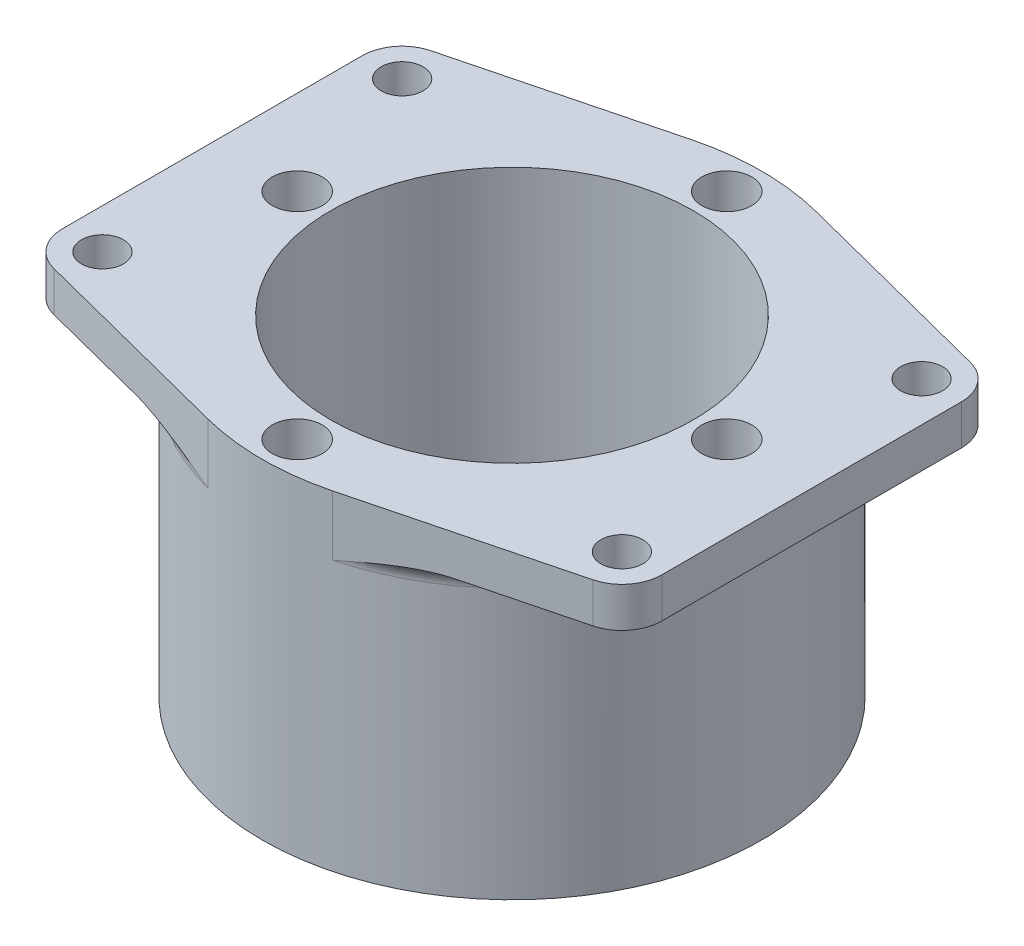
SolidWorks part; units mm, degrees
ref_plane "Front Plane" through (0, 0, 0) normal (0, 0, 1) x (1, 0, 0)
ref_plane "Top Plane" through (0, 0, 0) normal (0, 1, 0) x (1, 0, 0)
ref_plane "Right Plane" through (0, 0, 0) normal (1, 0, 0) x (0, 0, -1)
sketch "Sketch1" plane through (0, 0, 0) normal (0, 1, 0) x (1, 0, 0)
  circle A0 centre (0, 0) radius 25
  circle A1 centre (0, 0) radius 18.15 construction
  circle A2 centre (0, 0) radius 14 construction
  circle A3 centre (0, 14) radius 2.1
  circle A4 centre (14, 0) radius 2.1
  circle A5 centre (0, -14) radius 2.1
  circle A6 centre (-14, 0) radius 2.1
  point P16 (0, 0)
  dimension "D1" = 36.3
  dimension "D2" = 50
  dimension "D4" = 4.2
  dimension "D5" = 28
  dimension "D3" = 4
extrude "Boss-Extrude1" add sketch "Sketch1" along normal blind 3
sketch "Sketch2" plane through (0, 3, 0) normal (0, 1, 0) x (1, 0, 0)
  circle A0 centre (0, 0) radius 25
  circle A1 centre (0, 0) radius 18.15
  dimension "D1" = 50
  dimension "D2" = 36.3
extrude "Boss-Extrude2" add sketch "Sketch2" along normal blind 30
sketch "Sketch4" plane through (0, 33, 0) normal (0, 1, 0) x (1, 0, 0)
  circle A0 centre (0, 0) radius 21.5 construction
  circle A1 centre (0, 21.5) radius 2.5
  circle A2 centre (21.5, 0) radius 2.5
  circle A3 centre (0, -21.5) radius 2.5
  circle A4 centre (-21.5, 0) radius 2.5
  point P14 (0, 0)
  dimension "D1" = 5
  dimension "D2" = 43
  dimension "D3" = 4
extrude "Cut-Extrude1" cut sketch "Sketch4" against normal blind 8
sketch "Sketch5" plane through (0, 3, 0) normal (0, 1, 0) x (1, 0, 0)
  circle A0 centre (0, 0) radius 11.1
  dimension "D1" = 22.2
extrude "Cut-Extrude2" cut sketch "Sketch5" against normal blind 2
sketch "Sketch6" plane through (0, 1, 0) normal (0, 1, 0) x (1, 0, 0)
  circle A0 centre (0, 0) radius 4.5
  dimension "D1" = 9
extrude "Cut-Extrude3" cut sketch "Sketch6" against normal blind 2
sketch "Sketch7" plane through (0, 33, 0) normal (0, 1, 0) x (1, 0, 0)
  line L0 (0, 0) -> (-26, 0) construction
  line L1 (26, -15) -> (-26, -15) construction
  line L2 (26, -15) -> (26, 15) construction
  line L3 (26, 15) -> (-26, 15) construction
  line L4 (-26, -15) -> (-26, 15) construction
  line L5 (26, -15) -> (-26, 15) construction
  line L6 (26, 15) -> (-26, -15) construction
  line L9 (0, 15) -> (0, -15) construction
  line L10 (-26.9957, 18.8741) -> (-6.2232, 24.213)
  line L11 (-30, 15) -> (-30, -15)
  line L12 (30, 15) -> (30, -15)
  line L13 (26.9957, 18.8741) -> (6.2232, 24.213)
  line L14 (26.9957, -18.8741) -> (6.2232, -24.213)
  line L15 (-26.9957, -18.8741) -> (-6.2232, -24.213)
  arc A2 (-26.9957, 18.8741) -> (-30, 15) centre (-26, 15) ccw
  circle A3 centre (-26, 15) radius 2.1
  circle A4 centre (0, 0) radius 25 construction
  circle A8 centre (0, 21.5) radius 2.5 construction
  circle A13 centre (0, 21.5) radius 2.5
  circle A15 centre (0, 0) radius 25
  circle A16 centre (26, 15) radius 2.1
  arc A17 (26.9957, 18.8741) -> (30, 15) centre (26, 15) cw
  arc A18 (26.9957, -18.8741) -> (30, -15) centre (26, -15) ccw
  circle A19 centre (26, -15) radius 2.1
  circle A20 centre (-26, -15) radius 2.1
  arc A21 (-26.9957, -18.8741) -> (-30, -15) centre (-26, -15) cw
  point P0 (0, 0)
  circle M17 centre (0, 0) radius 25
  dimension "D3" = 8
  dimension "D4" = 4.2
  dimension "D1" = 52
  dimension "D2" = 30
extrude "Boss-Extrude3" add sketch "Sketch7" against normal blind 4 contours A21 L15 L10 A2 L11 A3 A20 M17 | L14 A18 L12 A17 L13 A19 A16 M17 region at (-16.4752, 33, -21.0211) region at (16.4752, 33, -21.0211)
fillet "Fillet1" radius 2 2 edges at (25, 29, 0) (-25, 29, 0)
